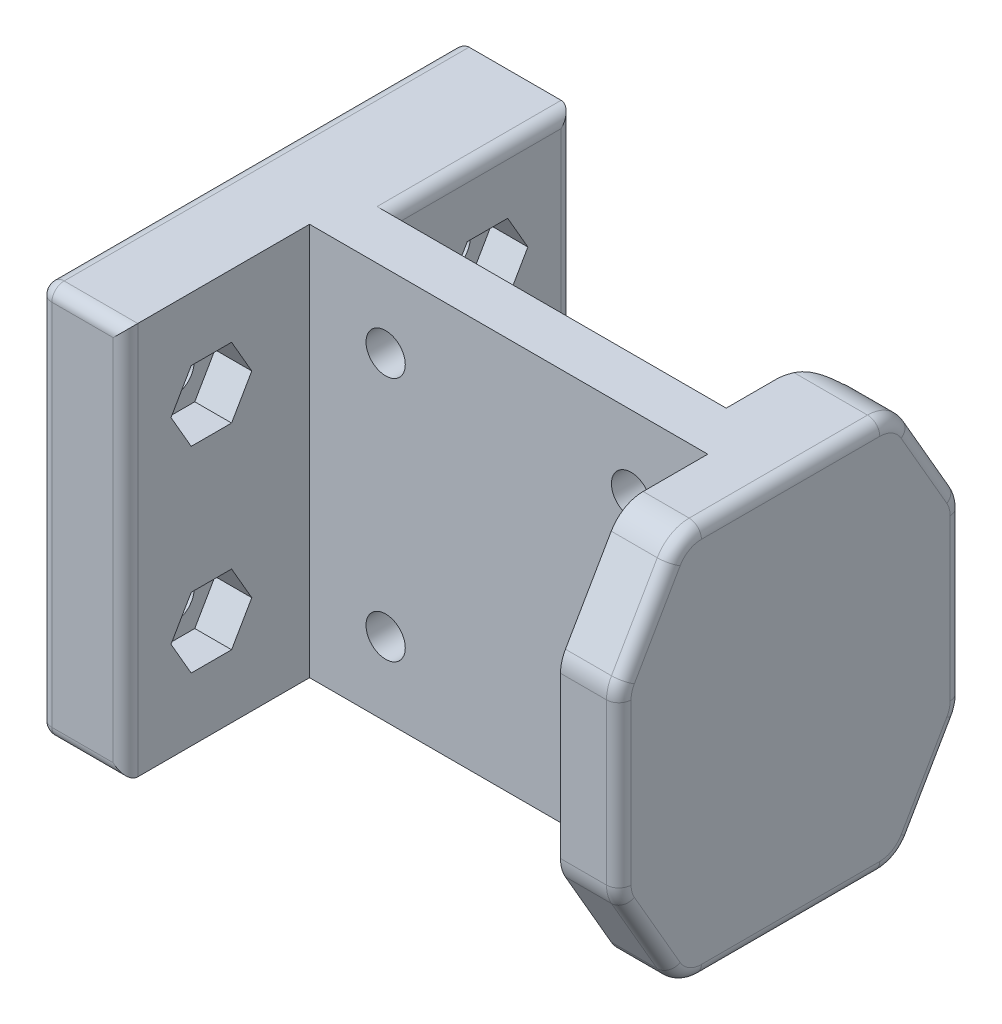
SolidWorks part; units mm, degrees
ref_plane "Спереди" through (0, 0, 0) normal (0, 0, 1) x (1, 0, 0)
ref_plane "Сверху" through (0, 0, 0) normal (0, 1, 0) x (1, 0, 0)
ref_plane "Справа" through (0, 0, 0) normal (1, 0, 0) x (0, 0, -1)
sketch "Эскиз1" plane through (0, 0, 0) normal (0, 0, 1) x (1, 0, 0)
  line L0 (0, 0) -> (36, 0)
  line L1 (0, 0) -> (0, 32)
  line L2 (36, 0) -> (36, 32)
  line L3 (0, 32) -> (36, 32)
  line L4 (18, 32) -> (18, 0) construction
  line L5 (36, 16) -> (0, 16) construction
  line L6 (8, 26) -> (8, 6) construction
  line L7 (8, 26) -> (28, 26) construction
  line L8 (28, 26) -> (28, 6) construction
  line L9 (28, 6) -> (8, 6) construction
  line L10 (8, 16) -> (28, 16) construction
  line L11 (18, 26) -> (18, 6) construction
  circle A0 centre (8, 26) radius 1.6
  circle A1 centre (28, 26) radius 1.6
  circle A2 centre (8, 6) radius 1.6
  circle A3 centre (28, 6) radius 1.6
  dimension "D1" = 20
  dimension "D2" = 20
  dimension "D3" = 3.2
  dimension "D4" = 3.2
  dimension "D5" = 3.2
  dimension "D6" = 3.2
  dimension "D7" = 32
  dimension "D8" = 36
extrude "Бобышка-Вытянуть1" add sketch "Эскиз1" along normal blind 4
sketch "Эскиз6" plane through (0, 32, 0) normal (0, 1, 0) x (1, 0, 0)
  line L0 (-5.2, -4) -> (-5.2, 24.8582) construction
  line L1 (36, -4) -> (0, -4) construction
  line L2 (36, -4) -> (36, 0) construction
  line L3 (-7.2, -4) -> (-7.2, 26.2382) construction
  dimension "D1" = 41.2
  dimension "D2" = 2
sketch "Эскиз7" plane through (0, 32, 0) normal (0, 1, 0) x (1, 0, 0)
  line L0 (0, 0) -> (-1.2, 0)
  line L1 (-1.2, 0) -> (-1.2, 15)
  line L3 (0, -4) -> (-1.2, -4)
  line L4 (-1.2, -4) -> (-1.2, -19)
  line L5 (-1.2, -19) -> (-5.2, -19)
  line L6 (-5.2, -19) -> (-5.2, 15)
  line L7 (-5.2, 15) -> (-1.2, 15)
  line L8 (-5.2, -4) -> (-5.2, 24.8582) construction
  line L9 (0, -4) -> (0, 0)
  dimension "D1" = 4
  dimension "D2" = 15
  dimension "D3" = 15
extrude "Бобышка-Вытянуть2" add sketch "Эскиз7" against normal up to surface (32 mm away) up to face at (18, 0, 2)
sketch "Эскиз8" plane through (-1.2, 0, 0) normal (1, 0, 0) x (0, 0, -1)
  line L0 (8, 24) -> (-12, 24) construction
  line L3 (8, 24) -> (8, 8) construction
  line L4 (-12, 24) -> (-12, 8) construction
  line L5 (8, 8) -> (-12, 8) construction
  line L6 (-4, 0) -> (-4, 32) construction
  line L7 (-4, 0) -> (-19, 0) construction
  line L8 (-19, 32) -> (-4, 32) construction
  circle A0 centre (8, 24) radius 1.6
  circle A1 centre (8, 8) radius 1.6
  circle A2 centre (-12, 8) radius 1.6
  circle A3 centre (-12, 24) radius 1.6
  dimension "D7" = 3.2
  dimension "D8" = 3.2
  dimension "D9" = 3.2
  dimension "D10" = 3.2
  dimension "D1" = 20
  dimension "D2" = 8
  dimension "D3" = 8
  dimension "D4" = 16
  dimension "D5" = 8
  dimension "D6" = 8
extrude "Вырез-Вытянуть1" cut sketch "Эскиз8" against normal through all
sketch "Sketch1" plane through (36, 0, 0) normal (1, 0, 0) x (0, 0, -1)
  line L4 (0, 0) -> (0, 32)
  line L5 (0, 32) -> (-4, 32)
  line L6 (-4, 32) -> (-4, 0)
  line L7 (-4, 0) -> (0, 0)
  line L8 (0, 0) -> (0, 32)
  line L9 (0, 32) -> (-4, 32)
  line L10 (-4, 32) -> (-4, 0)
  line L11 (-4, 0) -> (0, 0)
  dimension "D1" = 0
extrude "Boss-Extrude1" add sketch "Sketch1" along normal blind 3
sketch "Sketch2" plane through (0, 0, 0) normal (0, 0, -1) x (-1, 0, 0)
  line L0 (-39, 32) -> (-34, 32)
  line L1 (-39, 32) -> (-39, 0)
  line L2 (-34, 32) -> (-34, 0)
  line L3 (-39, 0) -> (-34, 0)
  line L4 (-39, 32) -> (1.2, 32) construction
  line L5 (1.2, 0) -> (-39, 0) construction
  dimension "D1" = 5
extrude "Boss-Extrude2" add sketch "Sketch2" along normal blind 12
sketch "Sketch3" plane through (39, 0, 0) normal (1, 0, 0) x (0, 0, -1)
  line L0 (0, 0) -> (0, 32) construction
  line L1 (0, 0) -> (0, 32) construction
  line L2 (0, 32) -> (7, 32) construction
  line L3 (12, 32) -> (-4, 32) construction
  line L4 (7, 32) -> (12, 23.3397) construction
  line L5 (12, 32) -> (12, 0) construction
  line L6 (0, 16) -> (12, 16) construction
  line L7 (12, 23.3397) -> (12, 8.6603) construction
  line L8 (7, 0) -> (12, 8.6603) construction
  line L9 (7, 32) -> (12, 32)
  line L10 (12, 32) -> (12, 23.3397)
  line L11 (12, 23.3397) -> (7, 32)
  line L12 (7, 0) -> (12, 8.6603) construction
  line L13 (0, 0) -> (7, 0) construction
  line L14 (12, 8.6603) -> (7, 0)
  line L15 (12, 0) -> (12, 8.6603)
  line L16 (7, 0) -> (12, 0)
  dimension "D1" = 120
  dimension "D2" = 7
extrude "Cut-Extrude1" cut sketch "Sketch3" against normal up to surface (5 mm away) up to face at (34, 16, -6)
sketch "Sketch6" plane through (39, 0, 0) normal (1, 0, 0) x (0, 0, -1)
  line L0 (7, 32) -> (0, 32) construction
  line L1 (7, 32) -> (0, 32) construction
  line L2 (7, 0) -> (0, 0) construction
  line L3 (7, 0) -> (0, 0) construction
  line L4 (0, 32) -> (0, 0) construction
  line L5 (-4, 32) -> (0, 32) construction
  line L6 (-4, 0) -> (0, 0) construction
  line L7 (-2, 32) -> (-2, 0) construction
  line L8 (12, 8.6603) -> (7, 0) construction
  line L9 (7, 32) -> (12, 23.3397) construction
  line L10 (12, 23.3397) -> (12, 8.6603) construction
  line L11 (7, 32) -> (12, 23.3397) construction
  line L12 (12, 23.3397) -> (12, 8.6603) construction
  line L13 (12, 8.6603) -> (7, 0) construction
  line L14 (-16, 8.6603) -> (-11, 0)
  line L15 (-16, 23.3397) -> (-16, 8.6603)
  line L16 (-11, 32) -> (-16, 23.3397)
  line L17 (-11, 32) -> (-4, 32)
  line L18 (-4, 32) -> (-4, 0)
  line L19 (-4, 0) -> (-11, 0)
extrude "Boss-Extrude5" add sketch "Sketch6" against normal blind 5
sketch "Sketch7" plane through (-1.2, 0, 0) normal (1, 0, 0) x (0, 0, -1)
  line L4 (0, 0) -> (15, 0)
  line L5 (15, 0) -> (15, 32)
  line L6 (15, 32) -> (0, 32)
  line L7 (0, 32) -> (0, 0)
  line L8 (0, 0) -> (15, 0)
  line L9 (15, 0) -> (15, 32)
  line L10 (15, 32) -> (0, 32)
  line L11 (0, 32) -> (0, 0)
  line L12 (-19, 0) -> (-4, 0)
  line L13 (-4, 0) -> (-4, 32)
  line L14 (-4, 32) -> (-19, 32)
  line L15 (-19, 32) -> (-19, 0)
  line L16 (-19, 0) -> (-4, 0)
  line L17 (-4, 0) -> (-4, 32)
  line L18 (-4, 32) -> (-19, 32)
  line L19 (-19, 32) -> (-19, 0)
  circle A0 centre (-12, 24) radius 1.6 construction
  circle A1 centre (-12, 8) radius 1.6 construction
  circle A2 centre (8, 24) radius 1.6 construction
  circle A3 centre (8, 8) radius 1.6 construction
  circle A4 centre (-12, 24) radius 1.6
  circle A5 centre (-12, 8) radius 1.6
  circle A6 centre (8, 24) radius 1.6
  circle A7 centre (8, 8) radius 1.6
  dimension "D1" = 0
  dimension "D2" = 0
extrude "Boss-Extrude6" add sketch "Sketch7" along normal blind 3
sketch "Sketch8" plane through (34, 0, 0) normal (-1, 0, 0) x (0, 0, 1)
  line L0 (-12, 23.3397) -> (-12, 8.6603) construction
  line L1 (-12, 8.6603) -> (-7, 0) construction
  line L2 (-7, 0) -> (0, 0) construction
  line L3 (0, 0) -> (0, 32) construction
  line L4 (0, 32) -> (-7, 32) construction
  line L5 (-7, 32) -> (-12, 23.3397) construction
  line L6 (4, 32) -> (4, 0) construction
  line L7 (4, 0) -> (11, 0) construction
  line L8 (11, 0) -> (16, 8.6603) construction
  line L9 (16, 8.6603) -> (16, 23.3397) construction
  line L10 (16, 23.3397) -> (11, 32) construction
  line L11 (11, 32) -> (4, 32) construction
  line L12 (-12, 23.3397) -> (-12, 8.6603)
  line L13 (-12, 8.6603) -> (-7, 0)
  line L14 (-7, 0) -> (0, 0)
  line L15 (0, 0) -> (0, 32)
  line L16 (0, 32) -> (-7, 32)
  line L17 (-7, 32) -> (-12, 23.3397)
  line L18 (4, 32) -> (4, 0)
  line L19 (4, 0) -> (11, 0)
  line L20 (11, 0) -> (16, 8.6603)
  line L21 (16, 8.6603) -> (16, 23.3397)
  line L22 (16, 23.3397) -> (11, 32)
  line L23 (11, 32) -> (4, 32)
extrude "Cut-Extrude2" cut sketch "Sketch8" against normal blind 0.25
sketch "Sketch9" plane through (1.8, 0, 0) normal (1, 0, 0) x (0, 0, -1)
  line L4 (0, 32) -> (0, 0)
  line L5 (0, 0) -> (15, 0)
  line L6 (15, 0) -> (15, 32)
  line L7 (15, 32) -> (0, 32)
  line L8 (0, 32) -> (0, 0)
  line L9 (0, 0) -> (15, 0)
  line L10 (15, 0) -> (15, 32)
  line L11 (15, 32) -> (0, 32)
  circle A0 centre (8, 24) radius 1.6 construction
  circle A1 centre (8, 8) radius 1.6 construction
  circle A2 centre (8, 24) radius 1.6
  circle A3 centre (8, 8) radius 1.6
  dimension "D1" = 0
extrude "Boss-Extrude7" add sketch "Sketch9" along normal blind 2.5
sketch "Sketch10" plane through (34.25, 0, 0) normal (-1, 0, 0) x (0, 0, 1)
  line L6 (-7, 32) -> (-12, 23.3397)
  line L7 (-12, 23.3397) -> (-12, 8.6603)
  line L8 (-12, 8.6603) -> (-7, 0)
  line L9 (-7, 0) -> (0, 0)
  line L10 (0, 0) -> (0, 32)
  line L11 (0, 32) -> (-7, 32)
  line L12 (-7, 32) -> (-12, 23.3397)
  line L13 (-12, 23.3397) -> (-12, 8.6603)
  line L14 (-12, 8.6603) -> (-7, 0)
  line L15 (-7, 0) -> (0, 0)
  line L16 (0, 0) -> (0, 32)
  line L17 (0, 32) -> (-7, 32)
  dimension "D1" = 0
extrude "Boss-Extrude8" add sketch "Sketch10" along normal blind 2.5
sketch "Sketch11" plane through (31.75, 0, 0) normal (-1, 0, 0) x (0, 0, 1)
  line L0 (-7, 32) -> (-12, 23.3397) construction
  line L1 (-12, 23.3397) -> (-12, 8.6603) construction
  line L2 (-12, 8.6603) -> (-7, 0) construction
  line L3 (-7, 32) -> (-12, 23.3397)
  line L4 (-12, 23.3397) -> (-12, 8.6603)
  line L5 (-12, 8.6603) -> (-7, 0)
  line L6 (-7, 32) -> (-7, 0)
extrude "Cut-Extrude3" cut sketch "Sketch11" against normal blind 2.5
fillet "Fillet2" radius 3 1 edges at (31.75, 16, -7)
fillet "Fillet4" radius 3 4 edges at (36.625, 0, -7) (36.625, 8.6603, -12) (36.625, 23.3397, -12) (36.625, 32, -7)
fillet "Fillet5" radius 3 4 edges at (36.625, 0, 11) (36.625, 8.6603, 16) (36.625, 23.3397, 16) (36.625, 32, 11)
fillet "Fillet9" radius 1 16 edges at (39, 8.6876, 15.8978) (39, 16, 16) (39, 23.3124, 15.8978) (39, 27.2679, 13.7321) (39, 31.5981, 10.7679) (39, 32, 2) (39, 31.5981, -6.7679) (39, 27.2679, -9.7321) (39, 23.3124, -11.8978) (39, 16, -12) (39, 8.6876, -11.8978) (39, 4.7321, -9.7321) (39, 0.4019, -6.7679) (39, 0, 2) (39, 0.4019, 10.7679) (39, 4.7321, 13.7321)
fillet "Fillet11" radius 1 4 edges at (-1.7, 32, 19) (1.8, 16, 19) (-1.7, 0, 19) (-5.2, 16, 19)
sketch "Sketch12" plane through (4.3, 0, 0) normal (1, 0, 0) x (0, 0, -1)
  line L0 (11.2909, 24) -> (4.7091, 24) construction
  line L1 (6.3546, 26.85) -> (4.7091, 24)
  line L2 (4.7091, 24) -> (6.3546, 21.15)
  line L3 (6.3546, 21.15) -> (9.6454, 21.15)
  line L4 (9.6454, 21.15) -> (11.2909, 24)
  line L5 (11.2909, 24) -> (9.6454, 26.85)
  line L6 (9.6454, 26.85) -> (6.3546, 26.85)
  line L7 (11.2909, 8) -> (4.7091, 8) construction
  line L8 (6.3546, 10.85) -> (4.7091, 8)
  line L9 (4.7091, 8) -> (6.3546, 5.15)
  line L10 (6.3546, 5.15) -> (9.6454, 5.15)
  line L11 (9.6454, 5.15) -> (11.2909, 8)
  line L12 (11.2909, 8) -> (9.6454, 10.85)
  line L13 (9.6454, 10.85) -> (6.3546, 10.85)
  circle A0 centre (8, 24) radius 2.85 construction
  circle A1 centre (8, 8) radius 2.85 construction
  dimension "D1" = 5.7
  dimension "D2" = 5.7
extrude "Cut-Extrude4" cut sketch "Sketch12" against normal blind 3
sketch "Sketch13" plane through (1.8, 0, 0) normal (1, 0, 0) x (0, 0, -1)
  line L0 (-8.7091, 24) -> (-15.2909, 24) construction
  line L1 (-15.2909, 24) -> (-13.6454, 21.15)
  line L2 (-13.6454, 21.15) -> (-10.3546, 21.15)
  line L3 (-10.3546, 21.15) -> (-8.7091, 24)
  line L4 (-8.7091, 24) -> (-10.3546, 26.85)
  line L5 (-10.3546, 26.85) -> (-13.6454, 26.85)
  line L6 (-13.6454, 26.85) -> (-15.2909, 24)
  line L7 (-15.2909, 8) -> (-13.6454, 5.15)
  line L8 (-13.6454, 5.15) -> (-10.3546, 5.15)
  line L9 (-10.3546, 5.15) -> (-8.7091, 8)
  line L10 (-8.7091, 8) -> (-10.3546, 10.85)
  line L11 (-10.3546, 10.85) -> (-13.6454, 10.85)
  line L12 (-13.6454, 10.85) -> (-15.2909, 8)
  line L13 (-8.7091, 8) -> (-15.2909, 8) construction
  circle A0 centre (-12, 24) radius 2.85 construction
  circle A1 centre (-12, 8) radius 2.85 construction
  dimension "D1" = 5.7
  dimension "D2" = 5.7
extrude "Cut-Extrude5" cut sketch "Sketch13" against normal blind 3
fillet "Fillet14" radius 1 8 edges at (-4.9071, 0.2929, 18.7071) (-4.9071, 31.7071, 18.7071) (4.3, 32, -7.5) (4.3, 0, -7.5) (4.3, 16, -15) (-5.2, 0, 1.5) (-5.2, 16, -15) (-5.2, 32, 1.5)
